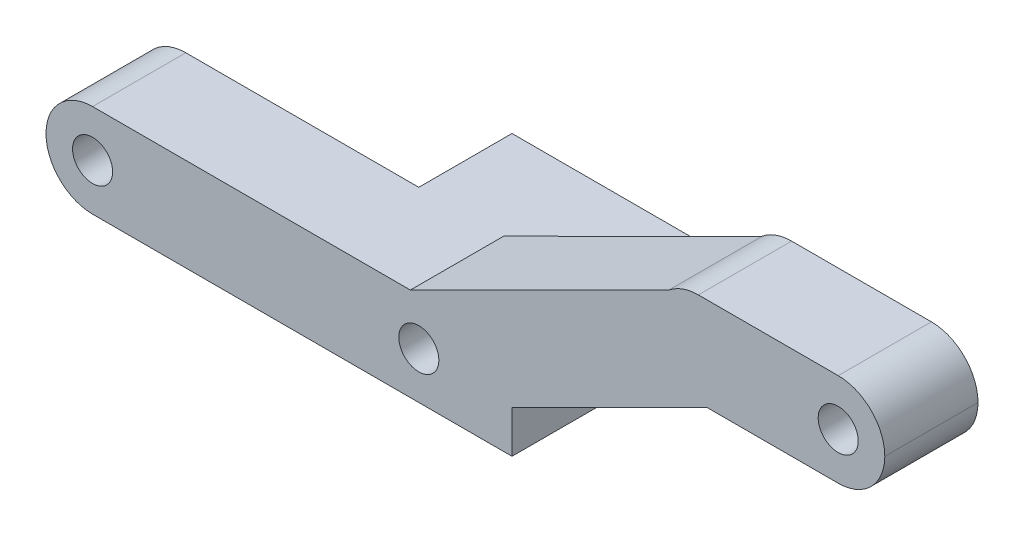
SolidWorks part; units mm, degrees
ref_plane "정면" through (0, 0, 0) normal (0, 0, 1) x (1, 0, 0)
ref_plane "윗면" through (0, 0, 0) normal (0, 1, 0) x (1, 0, 0)
ref_plane "우측면" through (0, 0, 0) normal (1, 0, 0) x (0, 0, -1)
sketch "스케치2" plane through (0, 0, 0) normal (0, 0, 1) x (1, 0, 0)
  line L0 (70, 27.5) -> (70, 17.5)
  line L1 (-20, 12.5) -> (19.0949, 12.5)
  line L2 (-20, 12.5) -> (-20, 2.5)
  line L3 (-20, 2.5) -> (20, 2.5)
  line L7 (50, 27.5) -> (70, 27.5)
  line L9 (50.9051, 17.5) -> (70, 17.5)
  line L13 (23.2009, 3.6589) -> (50.9051, 17.5)
  line L14 (19.0949, 12.5) -> (46.7991, 26.3411)
  arc A2 (20, 2.5) -> (23.2009, 3.6589) centre (20, 7.5) ccw
  arc A3 (50, 27.5) -> (46.7991, 26.3411) centre (50, 22.5) ccw
  dimension "D1" = 5
  dimension "D7" = 5
  dimension "D2" = 10
  dimension "D3" = 90
  dimension "D4" = 5
  dimension "D6" = 10
extrude "보스-돌출1" add sketch "스케치2" along normal blind 10
sketch "스케치3" plane through (0, 0, 10) normal (0, 0, 1) x (1, 0, 0)
  line L0 (19.0949, 12.5) -> (-20, 12.5) construction
  line L1 (10, 12.5) -> (30, 12.5)
  line L2 (10, 12.5) -> (10, 2.5)
  line L3 (10, 2.5) -> (30, 2.5)
  line L4 (30, 12.5) -> (30, 2.5)
  line L5 (10, 12.5) -> (30, 2.5) construction
  line L6 (10, 2.5) -> (30, 12.5) construction
  dimension "D2" = 20
extrude "보스-돌출2" add sketch "스케치3" against normal blind 20
fillet "필렛1" radius 5 4 edges at (-20, 12.5, 5) (-20, 2.5, 5) (70, 17.5, 5) (70, 27.5, 5)
sketch "스케치5" plane through (0, 0, -10) normal (0, 0, -1) x (-1, 0, 0)
  line L0 (-30, 12.5) -> (-10, 12.5) construction
  line L1 (-10, 12.5) -> (-10, 2.5) construction
  circle A0 centre (-20, 7.5) radius 2.15
  circle A1 centre (-65, 22.5) radius 2.15
  circle A2 centre (15, 7.5) radius 2.15
  dimension "D1" = 4.3
  dimension "D2" = 4.3
  dimension "D3" = 4.3
  dimension "D4" = 5
  dimension "D5" = 10
extrude "컷-돌출2" cut sketch "스케치5" against normal through all
sketch "스케치9" plane through (0, 2.5, 0) normal (0, -1, 0) x (1, 0, 0)
  line L1 (12.5, -7.5) -> (27.5, -7.5) construction
  line L2 (12.5, -7.5) -> (12.5, 7.5) construction
  line L3 (12.5, 7.5) -> (27.5, 7.5) construction
  line L4 (27.5, -7.5) -> (27.5, 7.5) construction
  line L5 (12.5, -7.5) -> (27.5, 7.5) construction
  line L6 (12.5, 7.5) -> (27.5, -7.5) construction
  circle A1 centre (12.5, 7.5) radius 1
  circle A2 centre (27.5, 7.5) radius 1
  circle A3 centre (12.5, -7.5) radius 1
  circle A4 centre (27.5, -7.5) radius 1
  dimension "D3" = 2
  dimension "D1" = 15
  dimension "D2" = 15
extrude "컷-돌출4" cut sketch "스케치9" against normal blind 8
sketch "스케치10" plane through (0, 2.5, 0) normal (0, -1, 0) x (1, 0, 0)
  line L0 (30, -10) -> (30, 10) construction
  line L1 (-15, 10) -> (30, 10) construction
  circle A0 centre (20, 0) radius 5
  dimension "D1" = 10
  dimension "D2" = 10
  dimension "D3" = 10
extrude "컷-돌출8" cut sketch "스케치10" along direction (0, 1, 0) on the side against the normal blind 2
